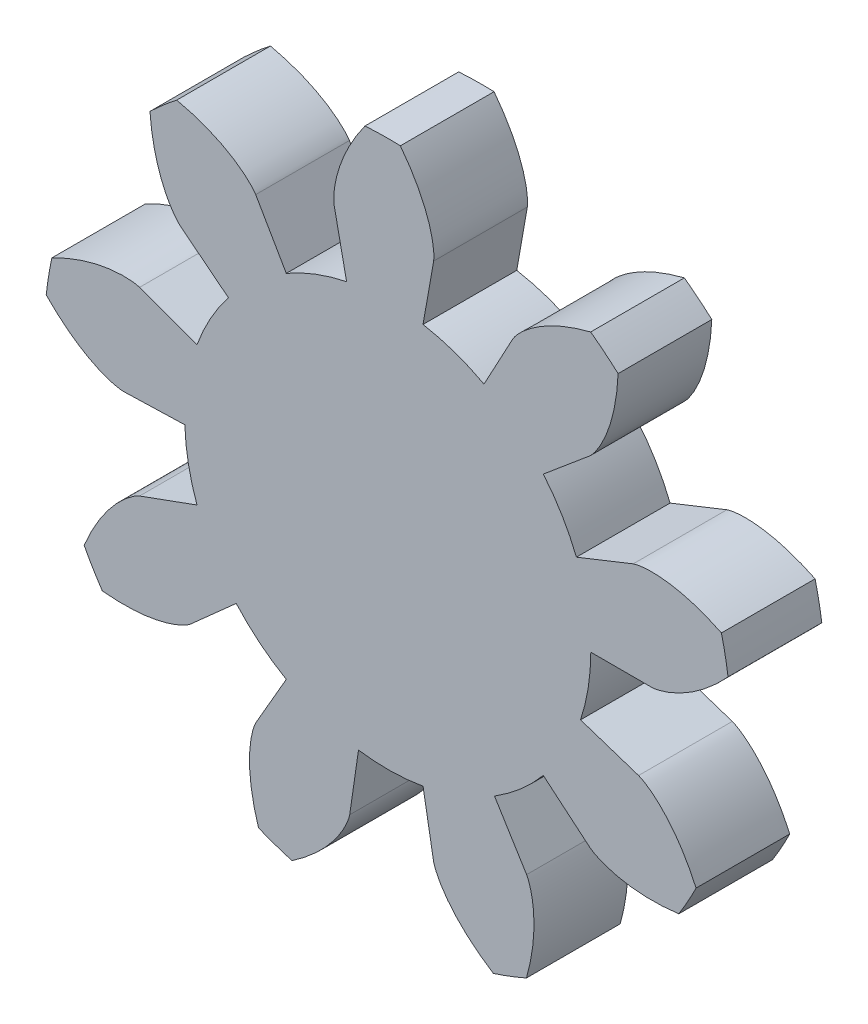
SolidWorks part; units mm, degrees
note: '?' marks a value the reader was unsure of.
ref_plane "Front" through (0, 0, 0) normal (0, 0, 1) x (1, 0, 0)
ref_plane "Top" through (0, 0, 0) normal (0, 1, 0) x (1, 0, 0)
ref_plane "Right" through (0, 0, 0) normal (1, 0, 0) x (0, 0, -1)
ref_axis "Axis1" through (0, 0, -80.9) along (0, 0, 1)?
sketch "Sketch1" plane through (0, 0, 0) normal (0, 0, 1) x (1, 0, 0)
  circle A0 centre (0, 0) radius 11.6417
  dimension "D1" = 23.2833
extrude "Boss-Extrude1" add sketch "Sketch1" against normal blind 3.175
sketch "Sketch2" plane through (0, 0, 0) normal (0, 0, 1) x (1, 0, 0)
  line L0 (3.4396, 0) -> (8.9506, 0)
  line L1 (0, 0) -> (7.8806, -1.2688) construction
  line L2 (3.2658, -1.0796) -> (8.4983, -2.8092)
  circle A0 centre (0, 0) radius 9.525 construction
  circle A1 centre (0, 0) radius 8.9506 construction
  circle A2 centre (0, 0) radius 6.8792 construction
  arc A3 (3.2658, -1.0796) -> (3.4396, 0) centre (0, 0) ccw
  spline S0 degree 4 poles (8.9506, 0) (8.9782, 0.0012) (9.0552, 0.0082) (9.2004, 0.0362) (9.4313, 0.102) (9.7208, 0.2167) (10.0779, 0.397) (10.4743, 0.6475) (10.8827, 0.9613) (11.2914, 1.337) (11.6692, 1.7437) (12.0167, 2.1764) (12.3503, 2.6538) (12.7232, 3.271) (13.1064, 4.0415) (13.4665, 4.9738) (13.7622, 6.0447) (13.9589, 7.1372) (14.0601, 8.2438) (14.0721, 9.3525) (13.9965, 10.4625) (13.8421, 11.5575) (13.6054, 12.6495) (13.3421, 13.5712) (13.0599, 14.3758) (12.8364, 14.9438) (12.6207, 15.4424) (12.4703, 15.7692) (12.2495, 16.2261) (12.07, 16.5652) (11.8879, 16.9037) (11.7894, 17.0708) (11.7277, 17.1794) knots 0 0 0 0 0 0.005604 0.015718 0.02996 0.048734 0.068727 0.096889 0.125051 0.153212 0.181374 0.209535 0.237696 0.271429 0.327752 0.384075 0.440398 0.496721 0.553044 0.609367 0.66569 0.722013 0.778336 0.834659 0.86282 0.890982 0.909091 0.931818 0.954545 0.977273 1 1 1 1 1 construction
  spline S1 degree 4 poles (8.9506, 0) (8.9782, 0.0012) (9.0552, 0.0082) (9.2004, 0.0362) (9.4313, 0.102) (9.7208, 0.2167) (10.0779, 0.397) (10.4743, 0.6475) (10.8827, 0.9613) (11.2914, 1.337) (11.6692, 1.7437) (12.0167, 2.1764) (12.3503, 2.6538) (12.7232, 3.271) (13.1064, 4.0415) (13.4665, 4.9738) (13.7622, 6.0447) (13.9589, 7.1372) (14.0601, 8.2438) (14.0721, 9.3525) (13.9965, 10.4625) (13.8421, 11.5575) (13.6054, 12.6495) (13.3421, 13.5712) (13.0599, 14.3758) (12.8364, 14.9438) (12.6712, 15.3258) (12.5864, 15.5145) (12.5527, 15.5882) knots 0 0 0 0 0 0.005604 0.015718 0.02996 0.048734 0.068727 0.096889 0.125051 0.153212 0.181374 0.209535 0.237696 0.271429 0.327752 0.384075 0.440398 0.496721 0.553044 0.609367 0.66569 0.722013 0.778336 0.834659 0.86282 0.890982 0.909091 0.909091 0.909091 0.909091 0.909091
  spline S2 degree 4 poles (8.4983, -2.8092) (8.5241, -2.819) (8.5951, -2.8499) (8.7241, -2.922) (8.9227, -3.057) (9.1616, -3.2567) (9.4441, -3.54) (9.7418, -3.9023) (10.0311, -4.3284) (10.3012, -4.8134) (10.5323, -5.3181) (10.7264, -5.838) (10.8933, -6.3959) (11.0536, -7.099) (11.1756, -7.9508) (11.225, -8.949) (11.1696, -10.0587) (11.0135, -11.1577) (10.7623, -12.2401) (10.4256, -13.2966) (10.0054, -14.3267) (9.5152, -15.318) (8.9477, -16.2805) (8.4084, -17.073) (7.888, -17.7484) (7.4975, -18.2175) (7.1362, -18.6232) (6.8908, -18.8863) (6.5378, -19.2509) (6.2609, -19.5165) (5.9818, -19.7807) (5.8358, -19.9085) (5.7431, -19.9922) knots 0 0 0 0 0 0.005604 0.015718 0.02996 0.048734 0.068727 0.096889 0.125051 0.153212 0.181374 0.209535 0.237696 0.271429 0.327752 0.384075 0.440398 0.496721 0.553044 0.609367 0.66569 0.722013 0.778336 0.834659 0.86282 0.890982 0.909091 0.931818 0.954545 0.977273 1 1 1 1 1 construction
  spline S3 degree 4 poles (8.4983, -2.8092) (8.5241, -2.819) (8.5951, -2.8499) (8.7241, -2.922) (8.9227, -3.057) (9.1616, -3.2567) (9.4441, -3.54) (9.7418, -3.9023) (10.0311, -4.3284) (10.3012, -4.8134) (10.5323, -5.3181) (10.7264, -5.838) (10.8933, -6.3959) (11.0536, -7.099) (11.1756, -7.9508) (11.225, -8.949) (11.1696, -10.0587) (11.0135, -11.1577) (10.7623, -12.2401) (10.4256, -13.2966) (10.0054, -14.3267) (9.5152, -15.318) (8.9477, -16.2805) (8.4084, -17.073) (7.888, -17.7484) (7.4975, -18.2175) (7.2207, -18.5283) (7.081, -18.681) (7.0259, -18.7404) knots 0 0 0 0 0 0.005604 0.015718 0.02996 0.048734 0.068727 0.096889 0.125051 0.153212 0.181374 0.209535 0.237696 0.271429 0.327752 0.384075 0.440398 0.496721 0.553044 0.609367 0.66569 0.722013 0.778336 0.834659 0.86282 0.890982 0.909091 0.909091 0.909091 0.909091 0.909091
  dimension "D1" = 19.05
  dimension "D2" = 17.9011
  dimension "D3" = 13.7583
  dimension "D5" = 6.8792
  dimension "D4" = 9.146
extrude "Cut-Extrude1" cut sketch "Sketch2" against normal through all and the other way through all
pattern_circular "CirPattern1" count 9 over 360 about axis through (0, 0, -3.175) along (0, 0, 1) of "Cut-Extrude1"
sketch "Sketch3" plane through (0, 0, 0) normal (0, 0, 1) x (1, 0, 0)
  circle A1 centre (0, 0) radius 6.8792 construction
  circle A2 centre (0, 0) radius 6.8792
extrude "Boss-Extrude2" add sketch "Sketch3" against normal up to surface (3.175 mm away) up to face at (0, 0, -3.175)
sketch "Sketch4" plane through (0, 0, 0) normal (0, 0, 1) x (1, 0, 0)
  circle A0 centre (0, 0) radius 9.525 construction
  circle A1 centre (0, 0) radius 9.525
surface "Pitch Circle" sketch "Sketch4"
ref_plane "Plane1" through (-0.1733, 11.6249, 0) normal (-0.0149, 0.9999, 0) x (0.9999, 0.0149, 0)
equation "\"P\"= \"P0\"'Diametral Pitch"
equation "\"N\"= \"N0\"'Number of Teeth"
equation "\"phi\"= \"phi0\"'Pressure Angle"
equation "\"a\"= 1 / \"P\"'Addendum"
equation "\"b\"= 1.25 / \"P\"'Dedendum"
equation "\"c\"= \"b\" - \"a\"'Clearance"
equation "\"dp\"= \"N\" / \"P\"'Pitch Circle Diameter"
equation "\"db\"= \"dp\" * cos ( \"phi\" )'Base Circle Diameter"
equation "\"alpha\"= sqr ( \"dp\" ^ 2 - \"db\" ^ 2 ) / \"db\" * 180deg / pi - \"phi\""
equation "\"D1@Sketch1\"=\"dp\"+2*\"a\""
equation "\"D3@Sketch2\"=\"dp\"-2*\"b\""
equation "\"D1@Sketch2\"=\"dp\""
equation "\"D2@Sketch2\"=\"db\""
equation "\"D4@Sketch2\"=360 / ( 4 * \"N\" ) - \"alpha\""
equation "\"D5@Sketch2\"=(\"dp\"-2*\"b\")/2"
equation "\"D1@CirPattern1\"=\"N\""
